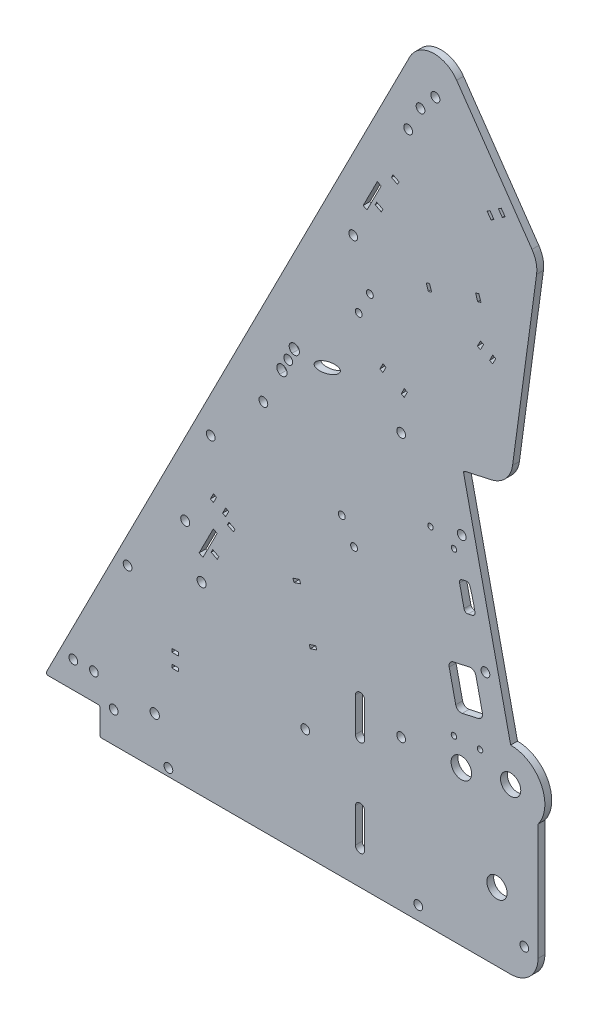
SolidWorks part; units mm, degrees
other "Markup1"
sketch "Sketch5"
ref_plane "Front Plane" through (0, 0, 0) normal (0, 0, 1) x (1, 0, 0)
ref_plane "Top Plane" through (0, 0, 0) normal (0, 1, 0) x (1, 0, 0)
ref_plane "Right Plane" through (0, 0, 0) normal (1, 0, 0) x (0, 0, -1)
sketch "Sketch1" plane through (0, 0, 0) normal (0, 0, 1) x (1, 0, 0)
  line L1 (228.6, -12.7) -> (228.6, 53.975)
  line L2 (178.7547, 351.4131) -> (0, 0)
  line L3 (228.6, 279.4) -> (178.7547, 351.4131)
  line L5 (0, 0) -> (25.4, 0)
  line L6 (25.4, 0) -> (25.4, -12.7)
  line L7 (25.4, -12.7) -> (228.6, -12.7)
  line L9 (215.9, 79.375) -> (193.9097, 178.5667)
  line L10 (193.9097, 178.5667) -> (215.6079, 183.377)
  line L11 (215.6079, 183.377) -> (228.6, 279.4)
  arc A0 (228.6, 53.975) -> (215.9, 79.375) centre (215.9, 63.5) ccw
  dimension "D7" = 12.7
  dimension "D8" = 76.2
  dimension "D10" = 31.75
  dimension "D2" = 292.1
  dimension "D3" = 25.4
  dimension "D4" = 215.9
  dimension "D5" = 394.2644
  dimension "D6" = 203.2
  dimension "D9" = 63.039
  dimension "D11" = 101.6
  dimension "D12" = 12.5
  dimension "D13" = 22.225
extrude "Boss-Extrude1" add sketch "Sketch1" along normal blind 3.175
sketch "Sketch2" plane through (0, 0, 3.175) normal (0, 0, 1) x (1, 0, 0)
  line L0 (178.7547, 351.4131) -> (0, 0) construction
  line L1 (25.4, -12.7) -> (228.6, -12.7) construction
  line L2 (215.9, 79.375) -> (193.9097, 178.5667) construction
  line L3 (193.9097, 178.5667) -> (215.6079, 183.377) construction
  line L4 (215.9, 79.375) -> (193.9097, 178.5667) construction
  line L5 (64.9432, 94.0578) -> (72.5445, 73.1732) construction
  line L6 (64.9432, 94.0578) -> (89.8317, 94.0578) construction
  line L10 (228.6, -12.7) -> (228.6, 53.975) construction
  circle A0 centre (64.9432, 94.0578) radius 2.0955
  circle A1 centre (180.975, 322.1643) radius 2.0955
  circle A2 centre (72.5445, 73.1732) radius 2.0955
  circle A3 centre (193.2078, 152.3944) radius 2.032
  circle A4 centre (215.9, 63.5) radius 4.699
  circle A7 centre (173.0375, -6.35) radius 2.032
  circle A8 centre (204.203, 102.7985) radius 2.032
  circle A26 centre (209.55, 19.05) radius 4.699
  arc A30 (228.6, 53.975) -> (215.9, 79.375) centre (215.9, 63.5) ccw construction
  circle A31 centre (165.1, 179.3875) radius 2.032
  dimension "D3" = 4.191
  dimension "D5" = 4.191
  dimension "D9" = 4.191
  dimension "D20" = 9.398
  dimension "D23" = 9.398
  dimension "D18" = 4.064
  dimension "D26" = 4.064
  dimension "D14" = 4.064
  dimension "D2" = 15.24
  dimension "D6" = 15.24
  dimension "D7" = 22.225
  dimension "D21" = 44.45
  dimension "D22" = 6.35
  dimension "D19" = 160.3375
  dimension "D24" = 44.45
  dimension "D25" = 6.35
  dimension "D27" = 25.4
  dimension "D28" = 50.8
  dimension "D29" = 6.35
  dimension "D17" = 6.35
  dimension "D33" = 55.5625
  dimension "D15" = 114.3
  dimension "D4" = 180.975
  dimension "D8" = 70
extrude "Cut-Extrude1" cut sketch "Sketch2" against normal through all
sketch "Sketch7" plane through (0, 0, 3.175) normal (0, 0, 1) x (1, 0, 0)
  line L0 (146.05, 3.175) -> (146.05, 19.05) construction
  line L1 (143.891, 3.175) -> (143.891, 19.05)
  line L2 (148.209, 3.175) -> (148.209, 19.05)
  line L3 (146.05, 47.625) -> (146.05, 63.5) construction
  line L4 (143.891, 47.625) -> (143.891, 63.5)
  line L5 (148.209, 47.625) -> (148.209, 63.5)
  line L6 (25.4, -12.7) -> (228.6, -12.7) construction
  line L12 (228.6, -12.7) -> (228.6, 53.975) construction
  line L13 (25.4, -12.7) -> (228.6, -12.7) construction
  arc A0 (143.891, 3.175) -> (148.209, 3.175) centre (146.05, 3.175) ccw
  arc A1 (148.209, 19.05) -> (143.891, 19.05) centre (146.05, 19.05) ccw
  arc A2 (143.891, 47.625) -> (148.209, 47.625) centre (146.05, 47.625) ccw
  arc A3 (148.209, 63.5) -> (143.891, 63.5) centre (146.05, 63.5) ccw
  circle A8 centre (50.8, 9.525) radius 2.159
  point P2 (146.05, 11.1125)
  point P9 (146.05, 55.5625)
  dimension "D1" = 4.318
  dimension "D5" = 4.318
  dimension "D2" = 15.875
  dimension "D3" = 15.875
  dimension "D4" = 44.45
  dimension "D6" = 95.25
  dimension "D7" = 82.55
  dimension "D8" = 15.875
  dimension "D9" = 22.225
extrude "Cut-Extrude2" cut sketch "Sketch7" against normal through all
sketch "Sketch10" plane through (0, 0, 3.175) normal (0, 0, 1) x (1, 0, 0)
  circle A1 centre (165.1, 57.15) radius 2.032
  circle A2 centre (120.65, 38.1) radius 2.032
  circle A3 centre (13.0465, 12.3347) radius 2.032
  circle A4 centre (22.5715, 12.3347) radius 2.032
  circle A5 centre (38.2114, 62.6398) radius 2.032
  dimension "D1" = 4.064
  dimension "D2" = 4.064
  dimension "D4" = 63.5
  dimension "D5" = 69.85
extrude "Cut-Extrude3" cut sketch "Sketch10" against normal up to next
fillet "Fillet1" radius 12.7 4 edges at (228.6, -12.7, 1.5875) (178.7547, 351.4131, 1.5875) (215.6079, 183.377, 1.5875) (228.6, 279.4, 1.5875)
fillet "Fillet2" radius 0.7937 4 edges at (25.4, -12.7, 1.5875) (25.4, 0, 1.5875) (193.9097, 178.5667, 1.5875) (0, 0, 1.5875)
sketch "Sketch12" plane through (0, 0, 3.175) normal (0, 0, 1) x (1, 0, 0)
  circle A0 centre (31.75, 1.5875) radius 2.032
  circle A1 centre (222.25, 1.5875) radius 2.032
  circle A2 centre (57.15, -9.2075) radius 2.032
  circle A3 centre (57.15, -9.2075) radius 2.286 construction
  dimension "D1" = 4.064
  dimension "D2" = 4.064
extrude "Cut-Extrude5" cut sketch "Sketch12" against normal through all
sketch "Sketch13" plane through (0, 0, 3.175) normal (0, 0, 1) x (1, 0, 0)
  line L2 (194.6847, 178.7385) -> (206.9592, 181.4597) construction
  line L5 (199.2434, 101.699) -> (189.6226, 145.0954) construction
  line L6 (189.6022, 69.9806) -> (201.7089, 70.5092) construction
  line L7 (186.8444, 98.9502) -> (199.2434, 101.699)
  line L8 (186.8444, 98.9502) -> (190.9676, 80.3518)
  line L9 (190.9676, 80.3518) -> (203.3665, 83.1006)
  line L10 (199.2434, 101.699) -> (203.3665, 83.1006)
  line L11 (189.6022, 69.9806) -> (190.9676, 80.3518) construction
  line L12 (201.7089, 70.5092) -> (203.3665, 83.1006) construction
  line L13 (215.9, 79.375) -> (194.0815, 177.7917) construction
  line L14 (178.7216, 148.5324) -> (189.6226, 145.0954) construction
  line L15 (195.1281, 134.9336) -> (193.4153, 134.5539)
  line L16 (192.209, 132.6604) -> (194.2706, 123.3612)
  line L17 (196.1641, 122.1549) -> (198.1091, 122.5861)
  line L18 (211.4332, 99.5233) -> (205.2337, 98.1489) construction
  line L19 (198.3765, 158.4184) -> (211.4332, 99.5233) construction
  circle A0 centre (189.6022, 69.9806) radius 1.27
  circle A1 centre (201.7089, 70.5092) radius 1.27
  circle A2 centre (178.7216, 148.5324) radius 1.27
  circle A3 centre (189.6226, 145.0954) radius 1.27
  arc A4 (199.3306, 124.402) -> (196.9796, 133.88) centre (134.9024, 113.4517) ccw
  arc A6 (199.4957, 103.5221) -> (189.2475, 149.7492) centre (134.9024, 113.4517) ccw construction
  arc A7 (195.1281, 134.9336) -> (196.9796, 133.88) centre (195.4717, 133.3837) cw
  arc A8 (198.1091, 122.5861) -> (199.3306, 124.402) centre (197.7655, 124.136) ccw
  arc A9 (194.2706, 123.3612) -> (196.1641, 122.1549) centre (195.8205, 123.7048) ccw
  arc A10 (193.4153, 134.5539) -> (192.209, 132.6604) centre (193.7589, 133.004) ccw
  point P26 (208.3335, 98.8361)
  point P31 (196.515, 135.2411)
  point P36 (194.6142, 121.8113)
  point P39 (191.8654, 134.2103)
  dimension "D7" = 2.54
  dimension "D16" = 1.5875
  dimension "D2" = 11.43
  dimension "D3" = 76.2
  dimension "D4" = 12.7
  dimension "D5" = 19.05
  dimension "D6" = 120
  dimension "D8" = 110
  dimension "D9" = 80
  dimension "D10" = 12.7
  dimension "D11" = 44.45
  dimension "D12" = 11.43
  dimension "D13" = 12.7
  dimension "D14" = 4.7625
  dimension "D15" = 38.1
extrude "Cut-Extrude6" cut sketch "Sketch13" against normal through all both and the other way through all
sketch "Sketch14" plane through (0, 0, 3.175) normal (0, 0, 1) x (1, 0, 0)
  line L0 (26.1937, -12.7) -> (215.9, -12.7) construction
  line L1 (228.6, 0) -> (228.6, 53.975) construction
  line L2 (112.7125, 182.5625) -> (101.1964, 159.9231) construction
  line L3 (169.1053, 332.4434) -> (0.5868, 1.1536) construction
  line L4 (112.7125, 182.5625) -> (136.864, 190.4279) construction
  line L5 (147.4827, 261.9243) -> (154.0469, 274.8287)
  line L6 (147.4827, 261.9243) -> (149.2654, 261.0175)
  line L7 (154.0469, 274.8287) -> (155.8295, 273.922)
  line L8 (149.2654, 261.0175) -> (155.8295, 273.922)
  line L9 (169.1053, 332.4434) -> (0.5868, 1.1536) construction
  line L10 (160.5905, 279.7801) -> (161.3102, 281.1951)
  line L11 (160.5905, 279.7801) -> (163.4204, 278.3406)
  line L12 (161.3102, 281.1951) -> (164.1402, 279.7556)
  line L13 (163.4204, 278.3406) -> (164.1402, 279.7556)
  line L14 (153.7897, 266.4104) -> (156.6196, 264.9709)
  line L15 (153.7897, 266.4104) -> (153.0699, 264.9954)
  line L16 (156.6196, 264.9709) -> (155.8998, 263.5559)
  line L17 (153.0699, 264.9954) -> (155.8998, 263.5559)
  line L19 (178.2697, 245.9923) -> (179.2404, 242.9693)
  line L20 (178.2697, 245.9923) -> (176.7582, 245.5069)
  line L21 (179.2404, 242.9693) -> (177.7289, 242.4839)
  line L22 (176.7582, 245.5069) -> (177.7289, 242.4839)
  line L24 (200.6096, 249.8308) -> (199.639, 252.8538)
  line L25 (200.6096, 249.8308) -> (202.1211, 250.3161)
  line L26 (199.639, 252.8538) -> (201.1505, 253.3391)
  line L27 (202.1211, 250.3161) -> (201.1505, 253.3391)
  line L34 (77.9534, 97.2255) -> (79.736, 96.3187)
  line L47 (77.9534, 97.2255) -> (71.3892, 84.3211)
  line L56 (79.736, 96.3187) -> (73.1718, 83.4143)
  line L57 (71.3892, 84.3211) -> (73.1718, 83.4143)
  line L58 (85.2167, 103.5918) -> (84.497, 102.1769)
  line L59 (85.2167, 103.5918) -> (88.0466, 102.1523)
  line L60 (84.497, 102.1769) -> (87.3269, 100.7374)
  line L61 (88.0466, 102.1523) -> (87.3269, 100.7374)
  line L62 (156.643, 199.3999) -> (158.0826, 202.2298)
  line L63 (156.643, 199.3999) -> (155.2281, 200.1197)
  line L64 (158.0826, 202.2298) -> (156.6676, 202.9496)
  line L65 (155.2281, 200.1197) -> (156.6676, 202.9496)
  line L66 (165.1328, 195.0814) -> (166.5723, 197.9113)
  line L67 (165.1328, 195.0814) -> (166.5478, 194.3617)
  line L68 (166.5723, 197.9113) -> (167.9873, 197.1916)
  line L69 (166.5478, 194.3617) -> (167.9873, 197.1916)
  line L78 (77.6961, 88.8072) -> (76.9764, 87.3922)
  line L79 (201.9154, 234.7497) -> (200.4759, 231.9198)
  line L80 (201.9154, 234.7497) -> (203.3303, 234.0299)
  line L81 (200.4759, 231.9198) -> (201.8908, 231.2)
  line L82 (203.3303, 234.0299) -> (201.8908, 231.2)
  line L83 (206.1357, 229.0407) -> (207.5752, 231.8707)
  line L84 (206.1357, 229.0407) -> (207.5507, 228.321)
  line L85 (207.5752, 231.8707) -> (208.9902, 231.1509)
  line L86 (207.5507, 228.321) -> (208.9902, 231.1509)
  line L88 (205.014, 288.3715) -> (206.821, 285.7609)
  line L89 (205.014, 288.3715) -> (206.3193, 289.275)
  line L90 (206.821, 285.7609) -> (208.1263, 286.6644)
  line L91 (206.3193, 289.275) -> (208.1263, 286.6644)
  line L92 (210.2352, 291.9855) -> (212.0422, 289.3749)
  line L93 (210.2352, 291.9855) -> (211.5405, 292.889)
  line L94 (212.0422, 289.3749) -> (213.3475, 290.2784)
  line L95 (211.5405, 292.889) -> (213.3475, 290.2784)
  line L96 (225.7968, 283.4499) -> (190.8675, 333.9133) construction
  line L97 (77.6961, 88.8072) -> (80.5261, 87.3677)
  line L98 (76.9764, 87.3922) -> (79.8063, 85.9527)
  line L99 (80.5261, 87.3677) -> (79.8063, 85.9527)
  line L100 (122.4534, 73.1037) -> (122.9512, 71.5963)
  line L101 (122.4534, 73.1037) -> (125.4682, 74.0993)
  line L102 (122.9512, 71.5963) -> (125.9661, 72.5919)
  line L103 (125.4682, 74.0993) -> (125.9661, 72.5919)
  line L104 (114.9173, 95.9228) -> (115.4151, 94.4154)
  line L105 (114.9173, 95.9228) -> (117.9322, 96.9185)
  line L106 (115.4151, 94.4154) -> (118.43, 95.411)
  line L107 (117.9322, 96.9185) -> (118.43, 95.411)
  line L108 (73.3338, 88.1438) -> (77.899, 97.1186) construction
  line L109 (75.1164, 87.2371) -> (79.6816, 96.2118) construction
  line L110 (76.2812, 89.5269) -> (86.5313, 84.313) construction
  line L111 (83.082, 102.8966) -> (93.3321, 97.6827) construction
  line L112 (121.934, 72.0825) -> (123.4755, 75.113) construction
  line L113 (127.9171, 72.8537) -> (123.4755, 75.113) construction
  line L114 (112.3753, 83.5081) -> (119.5388, 97.5909) construction
  line L115 (112.1491, 96.0767) -> (117.4079, 93.4017) construction
  line L116 (149.0052, 264.9173) -> (147.5544, 262.0651) construction
  line L117 (150.7878, 264.0106) -> (151.2099, 264.8403) construction
  line L118 (162.6248, 261.9162) -> (152.3747, 267.1302) construction
  line L119 (169.4256, 275.2859) -> (159.1755, 280.4999) construction
  line L120 (199.3876, 252.3597) -> (200.1584, 253.8749) construction
  line L121 (198.6169, 250.8445) -> (203.0585, 248.5852) construction
  line L122 (203.2698, 247.9167) -> (195.3067, 232.262) construction
  line L123 (180.2625, 244.9786) -> (175.0037, 247.6536) construction
  line L124 (178.1316, 240.7894) -> (185.2951, 254.8722) construction
  line L125 (190.7763, 226.1672) -> (185.5176, 228.8422) construction
  line L126 (58.7375, 39.6875) -> (61.9125, 39.6875)
  line L127 (58.7375, 39.6875) -> (58.7375, 38.1)
  line L128 (61.9125, 39.6875) -> (61.9125, 38.1)
  line L129 (58.7375, 38.1) -> (61.9125, 38.1)
  line L130 (58.7375, 33.3375) -> (61.9125, 33.3375)
  line L131 (58.7375, 33.3375) -> (58.7375, 31.75)
  line L132 (61.9125, 33.3375) -> (61.9125, 31.75)
  line L133 (58.7375, 31.75) -> (61.9125, 31.75)
  line L135 (78.0516, 111.4242) -> (76.6121, 108.5943)
  line L136 (78.0516, 111.4242) -> (79.4665, 110.7045)
  line L137 (76.6121, 108.5943) -> (78.027, 107.8745)
  line L138 (79.4665, 110.7045) -> (78.027, 107.8745)
  line L139 (82.2719, 105.7153) -> (83.7114, 108.5452)
  line L140 (82.2719, 105.7153) -> (83.6869, 104.9955)
  line L141 (83.7114, 108.5452) -> (85.1264, 107.8254)
  line L142 (83.6869, 104.9955) -> (85.1264, 107.8254)
  circle A0 centre (142.875, 247.65) radius 2.032
  circle A1 centre (112.7125, 182.5625) radius 2.032
  circle A2 centre (101.1964, 159.9231) radius 2.032
  circle A3 centre (150.594, 227.8985) radius 1.6 construction
  circle A4 centre (145.4254, 217.7376) radius 1.6 construction
  circle A5 centre (137.5592, 132.521) radius 1.6 construction
  circle A6 centre (143.2592, 122.6483) radius 1.6 construction
  circle A7 centre (150.594, 227.8985) radius 1.6
  circle A8 centre (145.4254, 217.7376) radius 1.6
  circle A9 centre (137.5592, 132.521) radius 1.6
  circle A10 centre (143.2592, 122.6483) radius 1.6
  arc A13 (0, 1.5875) -> (1.5875, 0) centre (1.5875, 1.5875) ccw construction
  ellipse E0 centre (109.8335, 176.9027) end of major axis (108.7539, 174.7802) minor radius 2.32 (108.7539, 174.7802) -> (110.9131, 179.0251) ccw construction
  ellipse E1 centre (109.8335, 176.9027) end of major axis (108.7539, 174.7802) minor radius 2.32 (108.7539, 174.7802) -> (110.9131, 179.0251) ccw
  ellipse E2 centre (130.8261, 188.4615) end of major axis (124.7883, 186.4952) minor radius 2.3812
  ellipse E3 centre (115.5915, 188.2223) end of major axis (114.5119, 186.0999) minor radius 2.32 (114.5119, 186.0999) -> (116.6711, 190.3448) ccw construction
  ellipse E4 centre (115.5915, 188.2223) end of major axis (114.5119, 186.0999) minor radius 2.32 (114.5119, 186.0999) -> (116.6711, 190.3448) ccw
  spline S0 degree 3 poles (1008.5248, 1963.4972) (-264.8214, -935.4578) (153.1817, 166.823) (110.3225, 179.2425) (110.1654, 179.2721) (109.6955, 179.3152) (109.3734, 179.2831) (108.9218, 179.1456) (108.7737, 179.0841) (108.4954, 178.9343) (108.365, 178.8464) (108.1219, 178.6442) (108.0097, 178.5297) (107.8134, 178.2839) (107.7278, 178.1512) (107.5834, 177.8672) (107.527, 177.7202) (107.4441, 177.4168) (107.4178, 177.2585) (107.3978, 176.9432) (107.4036, 176.7863) (107.4465, 176.4736) (107.4841, 176.3175) (107.5874, 176.0205) (107.6532, 175.8777) (107.8133, 175.6037) (107.9066, 175.4748) (116.556, 165.6387) (207.2632, 219.9049) (-1299.313, 1592.6452) knots -17.496982 -17.496982 -17.496982 -17.496982 0.0625 0.0625 0.125 0.125 0.25 0.25 0.3125 0.3125 0.375 0.375 0.4375 0.4375 0.5 0.5 0.5625 0.5625 0.625 0.625 0.6875 0.6875 0.75 0.75 0.8125 0.8125 0.875 0.875 6.02447 6.02447 6.02447 6.02447 only from (110.9131, 179.0251) to (108.7539, 174.7802) construction
  spline S1 degree 3 poles (110.9131, 179.0251) (110.7727, 179.0965) (110.6265, 179.1544) (110.3225, 179.2425) (110.1654, 179.2721) (109.6955, 179.3152) (109.3734, 179.2831) (108.9218, 179.1456) (108.7737, 179.0841) (108.4954, 178.9343) (108.365, 178.8464) (108.1219, 178.6442) (108.0097, 178.5297) (107.8134, 178.2839) (107.7278, 178.1512) (107.5834, 177.8672) (107.527, 177.7202) (107.4441, 177.4168) (107.4178, 177.2585) (107.3978, 176.9432) (107.4036, 176.7863) (107.4465, 176.4736) (107.4841, 176.3175) (107.5874, 176.0205) (107.6532, 175.8777) (107.8133, 175.6037) (107.9066, 175.4748) (108.2178, 175.121) (108.4736, 174.9228) (108.7539, 174.7802) knots 0 0 0 0 0.0625 0.0625 0.125 0.125 0.25 0.25 0.3125 0.3125 0.375 0.375 0.4375 0.4375 0.5 0.5 0.5625 0.5625 0.625 0.625 0.6875 0.6875 0.75 0.75 0.8125 0.8125 0.875 0.875 1 1 1 1
  spline S2 degree 3 poles (-1420.3275, 1467.1358) (182.122, 221.9776) (122.5576, 179.7991) (113.9875, 186.4501) (113.8729, 186.5577) (113.5583, 186.9155) (113.3974, 187.1901) (113.2413, 187.6401) (113.2046, 187.793) (113.1618, 188.1044) (113.1558, 188.2648) (113.176, 188.5797) (113.2018, 188.7347) (113.2848, 189.0394) (113.3426, 189.1891) (113.5563, 189.6095) (113.7586, 189.8627) (114.1212, 190.1647) (114.2542, 190.2544) (114.5324, 190.4041) (114.6775, 190.4645) (114.9798, 190.5567) (115.1369, 190.5882) (115.4499, 190.6199) (115.6074, 190.6207) (115.9244, 190.5918) (116.0795, 190.5623) (127.2954, 187.3224) (125.1094, 104.0575) (-1840.7764, 595.1392) knots -4.189038 -4.189038 -4.189038 -4.189038 0.0625 0.0625 0.125 0.125 0.25 0.25 0.3125 0.3125 0.375 0.375 0.4375 0.4375 0.5 0.5 0.625 0.625 0.6875 0.6875 0.75 0.75 0.8125 0.8125 0.875 0.875 0.9375 0.9375 5.517452 5.517452 5.517452 5.517452 only from (114.5119, 186.0999) to (116.6711, 190.3448) construction
  spline S3 degree 3 poles (114.5119, 186.0999) (114.3711, 186.1715) (114.2359, 186.2574) (113.9875, 186.4501) (113.8729, 186.5577) (113.5583, 186.9155) (113.3974, 187.1901) (113.2413, 187.6401) (113.2046, 187.793) (113.1618, 188.1044) (113.1558, 188.2648) (113.176, 188.5797) (113.2018, 188.7347) (113.2848, 189.0394) (113.3426, 189.1891) (113.5563, 189.6095) (113.7586, 189.8627) (114.1212, 190.1647) (114.2542, 190.2544) (114.5324, 190.4041) (114.6775, 190.4645) (114.9798, 190.5567) (115.1369, 190.5882) (115.4499, 190.6199) (115.6074, 190.6207) (115.9244, 190.5918) (116.0795, 190.5623) (116.3815, 190.4751) (116.53, 190.4166) (116.6711, 190.3448) knots 0 0 0 0 0.0625 0.0625 0.125 0.125 0.25 0.25 0.3125 0.3125 0.375 0.375 0.4375 0.4375 0.5 0.5 0.625 0.625 0.6875 0.6875 0.75 0.75 0.8125 0.8125 0.875 0.875 0.9375 0.9375 1 1 1 1
  point P63 (139.0462, 81.5294)
  point P175 (72.5479, 105.6501)
  point P178 (138.5599, 86.9205)
  point P179 (82.9794, 105.3554)
  point P180 (56.5445, 35.455)
  dimension "D1" = 4.064
  dimension "D15" = 3.175
  dimension "D2" = 195.2625
  dimension "D3" = 115.8875
  dimension "D4" = 85.725
  dimension "D5" = 260.35
  dimension "D6" = 25.4
  dimension "D7" = 4.7625
  dimension "D8" = 12.7
  dimension "D9" = 19.05
  dimension "D10" = 45
  dimension "D11" = 6.858
  dimension "D12" = 7.62
  dimension "D13" = 3.175
  dimension "D14" = 1.5875
  dimension "D16" = 1.5875
  dimension "D17" = 1.5875
  dimension "D18" = 9.525
  dimension "D19" = 47.625
  dimension "D20" = 38.1
  dimension "D21" = 6.858
  dimension "D22" = 7.62
  dimension "D23" = 1.5875
  dimension "D24" = 3.175
  dimension "D25" = 1.5875
  dimension "D26" = 4.7625
  dimension "D27" = 4.7625
  dimension "D28" = 1.5875
  dimension "D29" = 3.175
  dimension "D30" = 9.525
  dimension "D31" = 4.7625
  dimension "D32" = 4.7625
  dimension "D33" = 1.5875
  dimension "D34" = 3.175
  dimension "D35" = 6.35
  dimension "D36" = 12.7
  dimension "D37" = 1.5875
  dimension "D38" = 3.175
  dimension "D39" = 9.525
  dimension "D40" = 57.15
  dimension "D41" = 44.45
  dimension "D42" = 1.5875
  dimension "D43" = 4.7625
  dimension "D44" = 3.175
extrude "Cut-Extrude7" cut sketch "Sketch14" against normal up to next (3.175 mm away)
sketch "Sketch15" plane through (0, 0, 3.175) normal (0, 0, 1) x (1, 0, 0)
  line L0 (169.1053, 332.4434) -> (0.5868, 1.1536) construction
  circle A0 centre (76.7868, 134.1481) radius 2.032
  circle A1 centre (174.0994, 314.25) radius 2.032
  circle A2 centre (168.3414, 302.9303) radius 2.032
  circle A3 centre (174.0994, 314.25) radius 1.905 construction
  circle A4 centre (168.3414, 302.9303) radius 1.905 construction
  dimension "D1" = 4.064
  dimension "D4" = 4.064
  dimension "D2" = 7.62
  dimension "D3" = 76.2
extrude "Cut-Extrude8" cut sketch "Sketch15" against normal through all
fillet "Fillet3" radius 2.54 4 edges at (199.2434, 101.699, 1.5875) (186.8444, 98.9502, 1.5875) (190.9676, 80.3518, 1.5875) (203.3665, 83.1006, 1.5875)
sketch "Sketch16" plane through (0, 0, 3.175) normal (0, 0, 1) x (1, 0, 0)
  line L0 (228.6, 0) -> (228.6, 53.975) construction
  line L1 (26.1937, -12.7) -> (215.9, -12.7) construction
  circle A0 centre (193.04, 58.801) radius 4.7625
  dimension "D1" = 9.525
  dimension "D2" = 35.56
  dimension "D3" = 71.501
extrude "Cut-Extrude9" cut sketch "Sketch16" against normal through all
equation "\"D6@Sketch2\"=\"D2@Sketch2\""
